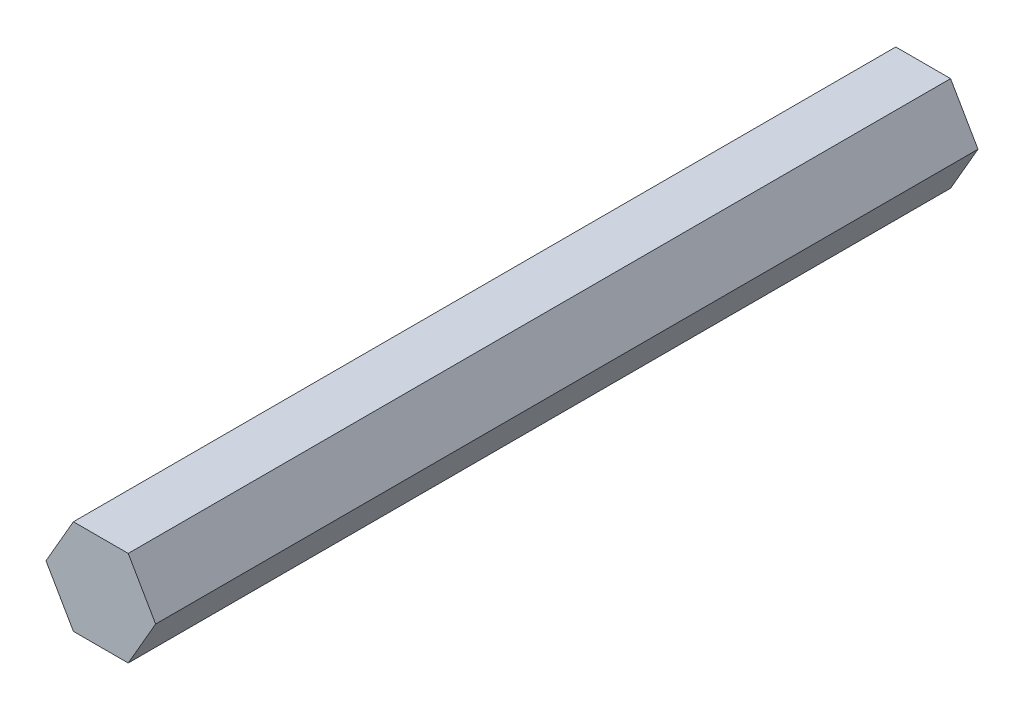
SolidWorks part; units mm, degrees
ref_plane "Front Plane" through (0, 0, 0) normal (0, 0, 1) x (1, 0, 0)
ref_plane "Top Plane" through (0, 0, 0) normal (0, 1, 0) x (1, 0, 0)
ref_plane "Right Plane" through (0, 0, 0) normal (1, 0, 0) x (0, 0, -1)
sketch "Sketch1" plane through (0, 0, 0) normal (0, 0, 1) x (1, 0, 0)
  line L1 (7.3323, 0) -> (3.6662, 6.35)
  line L2 (3.6662, 6.35) -> (-3.6662, 6.35)
  line L3 (-3.6662, 6.35) -> (-7.3323, 0)
  line L4 (-7.3323, 0) -> (-3.6662, -6.35)
  line L5 (-3.6662, -6.35) -> (3.6662, -6.35)
  line L6 (3.6662, -6.35) -> (7.3323, 0)
  circle A0 centre (0, 0) radius 6.35 construction
extrude "Boss-Extrude1" add sketch "Sketch1" along normal blind 110
